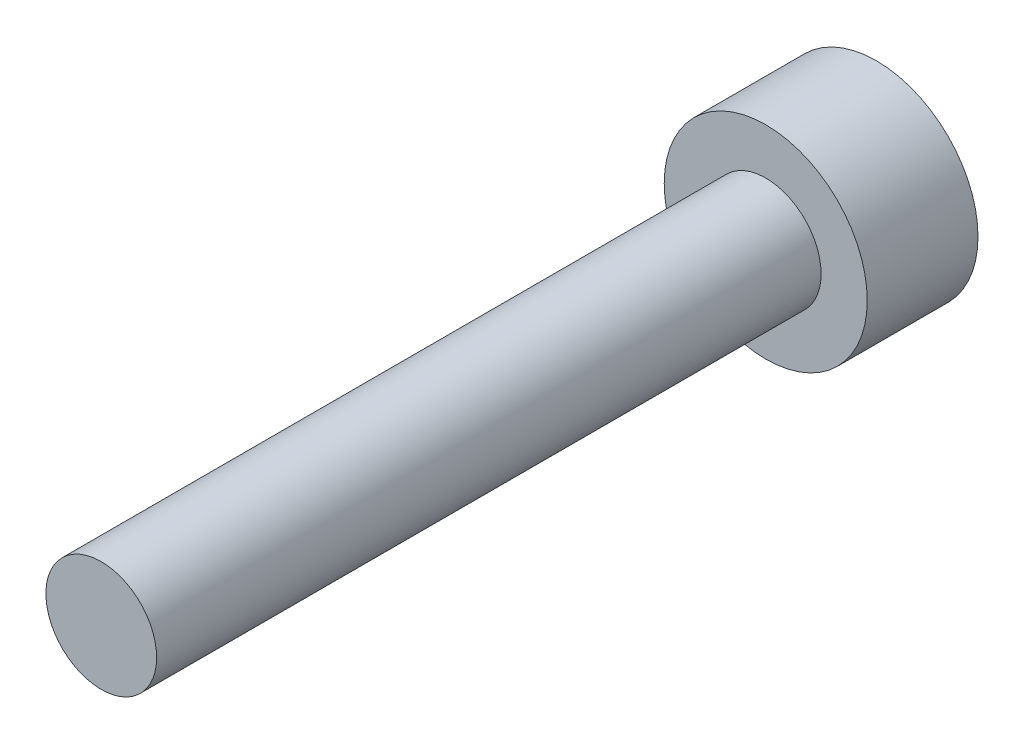
SolidWorks part; units mm, degrees
ref_plane "Front Plane" through (0, 0, 0) normal (0, 0, 1) x (1, 0, 0)
ref_plane "Top Plane" through (0, 0, 0) normal (0, 1, 0) x (1, 0, 0)
ref_plane "Right Plane" through (0, 0, 0) normal (1, 0, 0) x (0, 0, -1)
sketch "S01 - Head" plane through (0, 0, 0) normal (0, 0, 1) x (1, 0, 0)
  circle A0 centre (0, 0) radius 2.75
  dimension "D1" = 5.5
extrude "01 - Head" add sketch "S01 - Head" along normal blind 3 from offset 3 offset against normal yes
sketch "S02 - Nominal shank" plane through (0, 0, 0) normal (0, 0, 1) x (1, 0, 0)
  circle A0 centre (0, 0) radius 1.5
  dimension "D1" = 3
extrude "02 - Nominal shank" add sketch "S02 - Nominal shank" along normal blind 18
sketch "S03 - Hex key socket" plane through (0, 0, 0) normal (0, 0, 1) x (1, 0, 0)
  line L0 (1.4434, 0) -> (0.7217, 1.25)
  line L1 (0.7217, 1.25) -> (-0.7217, 1.25)
  line L2 (-0.7217, 1.25) -> (-1.4434, 0)
  line L3 (-1.4434, 0) -> (-0.7217, -1.25)
  line L4 (-0.7217, -1.25) -> (0.7217, -1.25)
  line L5 (0.7217, -1.25) -> (1.4434, 0)
  dimension "D1" = 0.7217
  dimension "D2" = 1.4434
  dimension "D3" = 0.7217
  dimension "D4" = 1.4434
  dimension "D5" = 1.25
  dimension "D6" = 1.25
extrude "03 - Hex key socket" cut sketch "S03 - Hex key socket" along normal blind 1.75 from offset 3.1 offset against normal yes
